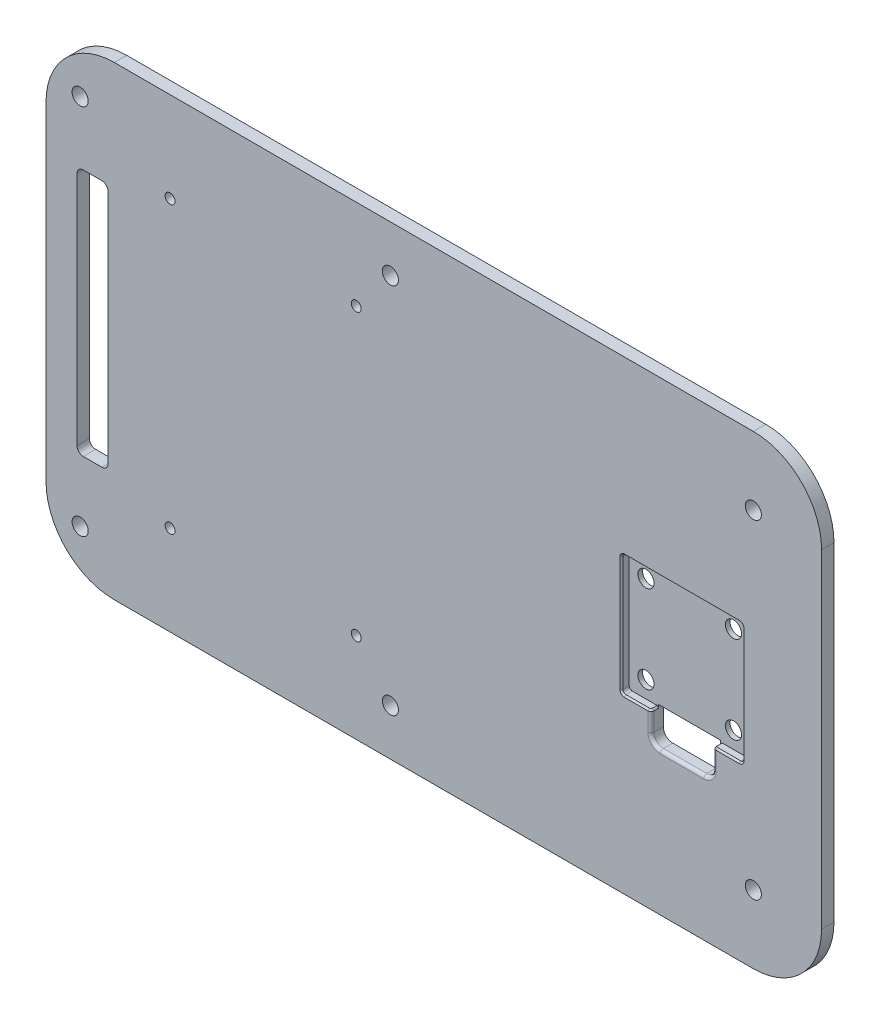
SolidWorks part; units mm, degrees
ref_plane "前视基准面" through (0, 0, 0) normal (0, 0, 1) x (1, 0, 0)
ref_plane "上视基准面" through (0, 0, 0) normal (0, 1, 0) x (1, 0, 0)
ref_plane "右视基准面" through (0, 0, 0) normal (1, 0, 0) x (0, 0, -1)
other "Configuration Table"
sketch "草图1" plane through (0, 0, 0) normal (0, 0, 1) x (1, 0, 0)
  line L0 (-1113.7626, 0) -> (48886.2374, 0) construction
  line L1 (-103, -75) -> (103, -75)
  line L2 (-125, -53) -> (-125, 53)
  line L3 (-103, 75) -> (103, 75)
  line L4 (125, -53) -> (125, 53)
  line L5 (-125, -75) -> (125, 75) construction
  line L6 (-125, 75) -> (125, -75) construction
  line L7 (-64, -1009.8705) -> (-64, 48990.1295) construction
  line L8 (-55, -1000) -> (-55, 49000) construction
  line L9 (-113, -40) -> (-107, -40)
  line L10 (-115, -38) -> (-115, 38)
  line L11 (-113, 40) -> (-107, 40)
  line L12 (-105, -38) -> (-105, 38)
  line L13 (-115, -40) -> (-105, 40) construction
  line L14 (-115, 40) -> (-105, -40) construction
  line L16 (-89, -50) -> (-21, -50) construction
  line L17 (-89, -50) -> (-89, 50) construction
  line L18 (-89, 50) -> (-21, 50) construction
  line L19 (-21, -50) -> (-21, 50) construction
  line L20 (-89, -50) -> (-21, 50) construction
  line L21 (-89, 50) -> (-21, -50) construction
  line L22 (70, -29) -> (90, -29)
  line L23 (70, -29) -> (70, -19)
  line L24 (70, -19) -> (90, -19)
  line L25 (90, -29) -> (90, -19)
  line L26 (70, -29) -> (90, -19) construction
  line L27 (70, -19) -> (90, -29) construction
  arc A0 (103, 75) -> (125, 53) centre (103, 53) cw
  arc A1 (103, -75) -> (125, -53) centre (103, -53) ccw
  arc A2 (-103, -75) -> (-125, -53) centre (-103, -53) cw
  arc A3 (-125, 53) -> (-103, 75) centre (-103, 53) cw
  circle A4 centre (-114, 60) radius 2.6
  circle A5 centre (-114, -60) radius 2.6
  circle A6 centre (-14, -60) radius 2.6
  circle A7 centre (-14, 60) radius 2.6
  arc A8 (-107, -40) -> (-105, -38) centre (-107, -38) ccw
  arc A9 (-113, -40) -> (-115, -38) centre (-113, -38) cw
  arc A10 (-105, 38) -> (-107, 40) centre (-107, 38) ccw
  arc A11 (-115, 38) -> (-113, 40) centre (-113, 38) cw
  circle A12 centre (-85, 46) radius 1.6
  circle A13 centre (-25, 46) radius 1.6
  circle A14 centre (-25, -46) radius 1.6
  circle A15 centre (-85, -46) radius 1.6
  circle A16 centre (103, 53) radius 2.6
  circle A17 centre (103, -53) radius 2.6
  point P0 (0, 0)
  point P30 (-110, 0)
  point P57 (-55, 0)
  point P62 (80, -29)
  point P63 (80, -24)
  dimension "D3" = 22
  dimension "D4" = 5.2
  dimension "D6" = 11
  dimension "D7" = 15
  dimension "D8" = 120
  dimension "D12" = 2
  dimension "D13" = 3.2
  dimension "D14" = 92
  dimension "D15" = 60
  dimension "D23" = 5.2
  dimension "D1" = 150
  dimension "D2" = 250
  dimension "D5" = 50
  dimension "D9" = 10
  dimension "D10" = 10
  dimension "D11" = 80
  dimension "D16" = 70
  dimension "D17" = 68
  dimension "D18" = 100
  dimension "D19" = 20
  dimension "D20" = 10
  dimension "D21" = 24
  dimension "D22" = 70
extrude "凸台-拉伸1" add sketch "草图1" along normal blind 4
sketch "草图2" plane through (0, 0, 4) normal (0, 0, 1) x (1, 0, 0)
  line L0 (-1000, 0) -> (49000, 0) construction
  line L1 (60.5, -19.5) -> (99.5, -19.5)
  line L2 (60.5, -19.5) -> (60.5, 19.5)
  line L3 (60.5, 19.5) -> (99.5, 19.5)
  line L4 (99.5, -19.5) -> (99.5, 19.5)
  line L5 (60.5, -19.5) -> (99.5, 19.5) construction
  line L6 (60.5, 19.5) -> (99.5, -19.5) construction
  line L7 (0, -1000) -> (0, 49000) construction
  point P0 (80, 0)
  dimension "D1" = 39
  dimension "D2" = 39
  dimension "D3" = 80
extrude "切除-拉伸1" cut sketch "草图2" against normal blind 2.5
fillet "圆角1" radius 3 2 edges at (70, -29, 2) (90, -29, 2)
fillet "圆角2" radius 1 9 edges at (80, -29, 4) (70.8787, -28.1213, 4) (70, -22.75, 4) (60.5, -19.5, 2.75) (99.5, -19.5, 2.75) (99.5, 19.5, 2.75) (60.5, 19.5, 2.75) (89.1213, -28.1213, 4) (90, -22.75, 4)
chamfer "倒角1" distance 0.5 angle 45 10 edges at (60.7929, -19.2071, 4) (99.2071, -19.2071, 4) (99.5, 0, 4) (99.2071, 19.2071, 4) (80, 19.5, 4) (60.7929, 19.2071, 4) (60.5, 0, 4) (94.75, -19.5, 4) (90, -19.5, 2.25) (90.2929, -19.5, 3.7071)
sketch "草图4" plane through (0, 0, 1.5) normal (0, 0, 1) x (1, 0, 0)
  line L0 (61.5, -18.5) -> (98.5, 18.5) construction
  line L1 (61.5, 18.5) -> (98.5, -18.5) construction
  line L2 (-920, 0) -> (49080, 0) construction
  line L3 (80, -1000) -> (80, 49000) construction
  line L10 (60.5, 18.5) -> (60.5, -18.5)
  line L11 (61.5, -19.5) -> (69.5, -19.5)
  line L12 (69.5, -19.5) -> (70, -20)
  line L13 (70, -20) -> (70, -19)
  line L14 (70, -19) -> (90, -19)
  line L15 (90, -19) -> (90, -20)
  line L16 (90, -20) -> (90.5, -19.5)
  line L17 (90.5, -19.5) -> (98.5, -19.5)
  line L18 (99.5, -18.5) -> (99.5, 18.5)
  line L19 (98.5, 19.5) -> (61.5, 19.5)
  line L20 (60.5, 18.5) -> (60.5, -18.5) construction
  line L21 (61.5, -19.5) -> (69.5, -19.5) construction
  line L22 (69.5, -19.5) -> (70, -20) construction
  line L23 (70, -20) -> (70, -19) construction
  line L24 (70, -19) -> (90, -19) construction
  line L25 (90, -19) -> (90, -20) construction
  line L26 (90, -20) -> (90.5, -19.5) construction
  line L27 (90.5, -19.5) -> (98.5, -19.5) construction
  line L28 (99.5, -18.5) -> (99.5, 18.5) construction
  line L29 (98.5, 19.5) -> (61.5, 19.5) construction
  circle A0 centre (65.9003, -14.0997) radius 2.6
  circle A2 centre (94.0997, -14.0997) radius 2.6
  circle A3 centre (94.0997, 14.0997) radius 2.6
  arc A4 (60.5, -18.5) -> (61.5, -19.5) centre (61.5, -18.5) ccw
  arc A5 (98.5, -19.5) -> (99.5, -18.5) centre (98.5, -18.5) ccw
  arc A6 (99.5, 18.5) -> (98.5, 19.5) centre (98.5, 18.5) ccw
  arc A7 (61.5, 19.5) -> (60.5, 18.5) centre (61.5, 18.5) ccw
  arc A8 (60.5, -18.5) -> (61.5, -19.5) centre (61.5, -18.5) ccw construction
  arc A9 (98.5, -19.5) -> (99.5, -18.5) centre (98.5, -18.5) ccw construction
  arc A10 (99.5, 18.5) -> (98.5, 19.5) centre (98.5, 18.5) ccw construction
  arc A11 (61.5, 19.5) -> (60.5, 18.5) centre (61.5, 18.5) ccw construction
  circle A12 centre (65.9003, 14.0997) radius 2.6
  point P19 (80, 0)
  dimension "D2" = 5.2
  dimension "D3" = 39.88
  dimension "D1" = 0
extrude "切除-拉伸2" cut sketch "草图4" against normal blind 2
